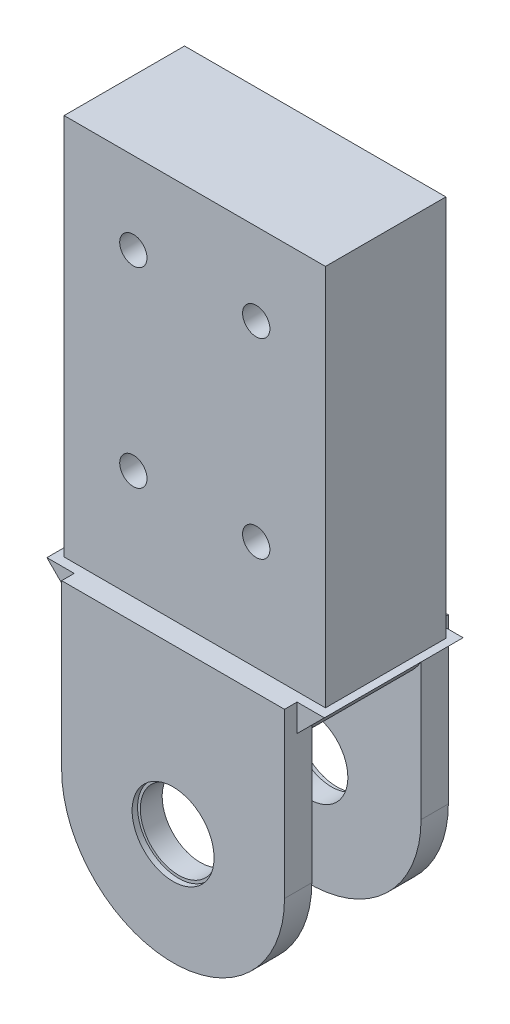
SolidWorks part; units mm, degrees
ref_plane "Front Plane" through (0, 0, 0) normal (0, 0, 1) x (1, 0, 0)
ref_plane "Top Plane" through (0, 0, 0) normal (0, 1, 0) x (1, 0, 0)
ref_plane "Right Plane" through (0, 0, 0) normal (1, 0, 0) x (0, 0, -1)
sketch "Sketch1" plane through (0, 0, 0) normal (0, 0, 1) x (1, 0, 0)
  line L0 (-25.4, 0) -> (-25.4, 100)
  line L1 (-25.4, 100) -> (25.4, 100)
  line L2 (25.4, 100) -> (25.4, 0)
  line L4 (-11.25, 85) -> (11.25, 85) construction
  line L5 (-11.25, 85) -> (-11.25, 50) construction
  line L6 (-11.25, 50) -> (11.25, 50) construction
  line L7 (11.25, 85) -> (11.25, 50) construction
  circle A0 centre (0, 0) radius 7
  arc A1 (-25.4, 0) -> (25.4, 0) centre (0, 0) ccw
  circle A2 centre (-11.25, 85) radius 2.5
  circle A3 centre (11.25, 85) radius 2.5
  circle A4 centre (11.25, 50) radius 2.5
  circle A5 centre (-11.25, 50) radius 2.5
  point P13 (0, 50)
  dimension "D1" = 14
  dimension "D4" = 5
  dimension "D2" = 50.8
  dimension "D3" = 100
  dimension "D5" = 35
  dimension "D6" = 15
  dimension "D7" = 22.5
extrude "Boss-Extrude1" add sketch "Sketch1" along normal blind 30
sketch "Sketch2" plane through (25.4, 0, 0) normal (1, 0, 0) x (0, 0, -1)
  line L0 (-30, -25.4) -> (0, -25.4) construction
  line L1 (-25, 20) -> (-5, 20)
  line L2 (-25, 20) -> (-25, -25.4)
  line L3 (-25, -25.4) -> (-5, -25.4)
  line L4 (-5, 20) -> (-5, -25.4)
  line L5 (-30, 0) -> (0, 0) construction
  point P8 (-15, 0)
  point P9 (-15, 20)
  dimension "D1" = 20
  dimension "D2" = 20
extrude "Cut-Extrude1" cut sketch "Sketch2" against normal through all
sketch "Sketch3" plane through (0, 0, 30) normal (0, 0, 1) x (1, 0, 0)
  circle A0 centre (0, 0) radius 7.5
  dimension "D1" = 15
extrude "Cut-Extrude2" cut sketch "Sketch3" against normal blind 1
sketch "Sketch4" plane through (0, 0, 0) normal (0, 0, -1) x (-1, 0, 0)
  circle A0 centre (0, 0) radius 7.5
  dimension "D1" = 15
extrude "Cut-Extrude3" cut sketch "Sketch4" against normal blind 1
sketch "Sketch5" plane through (25.4, 0, 0) normal (1, 0, 0) x (0, 0, -1)
  line L1 (-30, 100) -> (-27.7, 100)
  line L2 (-30, 100) -> (-30, 30)
  line L3 (-30, 30) -> (-27.7, 30)
  line L4 (-27.7, 100) -> (-27.7, 30)
  line L5 (0, 100) -> (-2.3, 100)
  line L6 (0, 100) -> (0, 30)
  line L7 (0, 30) -> (-2.3, 30)
  line L8 (-2.3, 100) -> (-2.3, 30)
  dimension "D1" = 70
  dimension "D2" = 25.4
extrude "Cut-Extrude4" cut sketch "Sketch5" against normal through all
sketch "Sketch6" plane through (0, 0, 30) normal (0, 0, 1) x (1, 0, 0)
  line L0 (-20.4, 0) -> (-20.4, 30)
  line L1 (-25.4, 30) -> (25.4, 30) construction
  line L3 (-25.4, 30) -> (25.4, 30) construction
  line L4 (20.4, 30) -> (20.4, 0)
  line L5 (-20.4, 30) -> (-25.4, 30)
  line L6 (-25.4, 30) -> (-25.4, -25.4)
  line L7 (-25.4, -25.4) -> (25.4, -25.4)
  line L8 (25.4, -25.4) -> (25.4, 30)
  line L9 (25.4, 30) -> (20.4, 30)
  arc A0 (-20.4, 0) -> (20.4, 0) centre (0, 0) ccw
  arc A1 (-25.4, 0) -> (25.4, 0) centre (0, 0) ccw construction
  point P19 (0, -25.4)
  dimension "D1" = 5
extrude "Cut-Extrude5" cut sketch "Sketch6" against normal through all
sketch "Sketch8" plane through (0, 100, 0) normal (0, 1, 0) x (1, 0, 0)
  line L0 (-25.4, -27.7) -> (-25.4, -2.3) construction
  line L1 (-23.925, -3.975) -> (23.925, -3.975)
  line L2 (-23.925, -3.975) -> (-23.925, -26.025)
  line L3 (-23.925, -26.025) -> (23.925, -26.025)
  line L4 (23.925, -3.975) -> (23.925, -26.025)
  line L6 (-25.4, -2.3) -> (25.4, -2.3)
  line L7 (-25.4, -2.3) -> (-25.4, -27.7)
  line L8 (-25.4, -27.7) -> (25.4, -27.7)
  line L9 (25.4, -2.3) -> (25.4, -27.7)
  point P5 (0, -3.975)
  point P10 (-25.4, -15)
  point P11 (-23.925, -15)
  dimension "D1" = 22.05
  dimension "D2" = 47.85
extrude "Cut-Extrude6" cut sketch "Sketch8" against normal up to surface (70 mm away) up to face at (0, 30, 1.15)
sketch "Sketch9" plane through (0, 30, 0) normal (0, 1, 0) x (1, 0, 0)
  line L0 (23.925, -3.975) -> (-23.925, -3.975) construction
  line L1 (-25.4, -2.3) -> (25.4, -2.3)
  line L2 (-25.4, -2.3) -> (-25.4, -27.7)
  line L3 (-25.4, -27.7) -> (25.4, -27.7)
  line L4 (25.4, -2.3) -> (25.4, -27.7)
  line L5 (-23.925, -3.975) -> (-23.925, -26.025) construction
  point P8 (0, -3.975)
  point P9 (0, -2.3)
  point P12 (-23.925, -15)
  point P13 (-25.4, -15)
  dimension "D1" = 25.4
  dimension "D2" = 50.8
extrude "Boss-Extrude2" add sketch "Sketch9" against normal blind 5
fillet "Fillet1" radius 10 2 edges at (20.4, 20, 15) (-20.4, 20, 15)
chamfer "Chamfer1" distance 5 angle 45 2 edges at (-25.4, 25, 15) (25.4, 25, 15)
